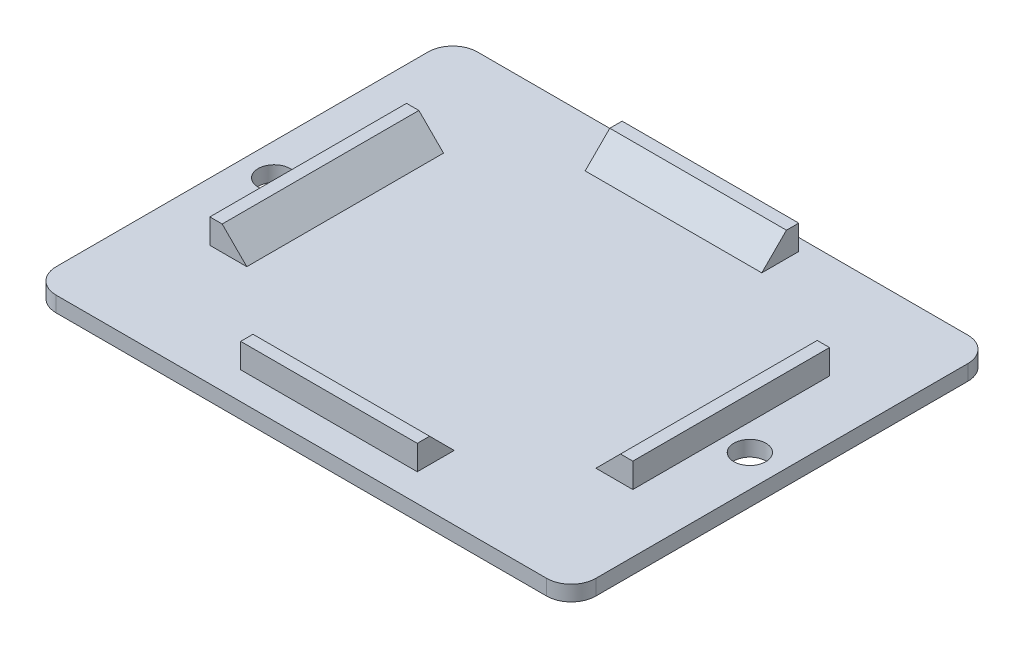
SolidWorks part; units mm, degrees
ref_plane "Plane XZ" through (0, 0, 0) normal (0, 0, 1) x (1, 0, 0)
ref_plane "Plane XY" through (0, 0, 0) normal (0, 1, 0) x (1, 0, 0)
ref_plane "Plane YZ" through (0, 0, 0) normal (1, 0, 0) x (0, 0, -1)
sketch "Sketch1" plane through (0, 0, 0) normal (0, 1, 0) x (1, 0, 0)
  line L0 (0, 22.225) -> (0, -22.225) construction
  line L1 (-28.3337, 22.225) -> (28.3337, 22.225)
  line L2 (-28.3337, 22.225) -> (-28.3337, -22.225)
  line L3 (-28.3337, -22.225) -> (28.3337, -22.225)
  line L4 (28.3337, 22.225) -> (28.3337, -22.225)
  dimension "D1" = 56.6674
  dimension "D2" = 44.45
extrude "Boss-Extrude1" add sketch "Sketch1" along normal blind 1.5875
sketch "Sketch2" plane through (0, 1.5875, 0) normal (0, 1, 0) x (1, 0, 0)
  line L0 (28.3337, 22.225) -> (-28.3337, 22.225) construction
  line L1 (-21.9837, 20.6375) -> (21.9837, 20.6375) construction
  line L2 (-21.9837, 20.6375) -> (-21.9837, -19.05) construction
  line L3 (-21.9837, -19.05) -> (21.9837, -19.05) construction
  line L4 (21.9837, 20.6375) -> (21.9837, -19.05) construction
  line L5 (28.3337, -22.225) -> (28.3337, 22.225) construction
  line L6 (-28.3337, 22.225) -> (-28.3337, -22.225) construction
  line L15 (-21.8059, 20.4597) -> (-21.8059, -18.8722)
  line L16 (-21.8059, -18.8722) -> (21.8059, -18.8722)
  line L17 (21.8059, 20.4597) -> (21.8059, -18.8722)
  line L18 (-21.8059, 20.4597) -> (21.8059, 20.4597)
  line L19 (-20.5359, 19.1897) -> (-20.5359, -17.6022)
  line L20 (-20.5359, -17.6022) -> (20.5359, -17.6022)
  line L21 (20.5359, 19.1897) -> (20.5359, -17.6022)
  line L22 (-20.5359, 19.1897) -> (20.5359, 19.1897)
  dimension "D1" = 43.9674
  dimension "D2" = 39.6875
  dimension "D3" = 1.5875
  dimension "D4" = 6.35
  dimension "D5" = 6.35
  dimension "D6" = 0.1778
  dimension "D7" = 1.27
extrude "Boss-Extrude2" add sketch "Sketch2" along normal blind 2.54
sketch "Sketch3" plane through (0, 1.5875, 0) normal (0, 1, 0) x (1, 0, 0)
  line L0 (-24.5237, 0) -> (24.5237, 0) construction
  circle A0 centre (-24.5237, 0) radius 1.651
  circle A1 centre (24.5237, 0) radius 1.651
  dimension "D1" = 3.302
  dimension "D2" = 3.302
  dimension "D3" = 49.0474
extrude "Cut-Extrude1" cut sketch "Sketch3" against normal through all
sketch "Sketch4" plane through (0, 1.5875, 0) normal (0, 1, 0) x (1, 0, 0)
  line L0 (27.8257, 21.717) -> (-27.8257, 21.717)
  line L1 (-27.8257, 21.717) -> (-27.8257, -21.717)
  line L2 (-27.8257, -21.717) -> (27.8257, -21.717)
  line L3 (27.8257, -21.717) -> (27.8257, 21.717)
  line L4 (-28.3337, 22.225) -> (-28.3337, -22.225)
  line L5 (-28.3337, -22.225) -> (28.3337, -22.225)
  line L6 (28.3337, -22.225) -> (28.3337, 22.225)
  line L7 (28.3337, 22.225) -> (-28.3337, 22.225)
  line L8 (-28.3337, 22.225) -> (-28.3337, -22.225)
  line L9 (-28.3337, -22.225) -> (28.3337, -22.225)
  line L10 (28.3337, -22.225) -> (28.3337, 22.225)
  line L11 (28.3337, 22.225) -> (-28.3337, 22.225)
  dimension "D1" = 0
  dimension "D2" = 0.508
extrude "Cut-Extrude2" cut sketch "Sketch4" against normal through all
fillet "Fillet1" radius 2.54 4 edges at (-27.8257, 0.7937, 21.717) (27.8257, 0.7937, 21.717) (27.8257, 0.7937, -21.717) (-27.8257, 0.7937, -21.717)
sketch "Sketch5" plane through (0, 1.5875, 0) normal (0, 1, 0) x (1, 0, 0)
  line L0 (-20.5359, 0.7937) -> (20.5359, 0.7937) construction
  line L1 (-21.8059, 20.4597) -> (-9.1059, 20.4597)
  line L2 (-21.8059, 20.4597) -> (-21.8059, 10.9347)
  line L3 (-21.8059, 10.9347) -> (-9.1059, 10.9347)
  line L4 (-9.1059, 20.4597) -> (-9.1059, 10.9347)
  line L5 (-20.5359, 19.1897) -> (-20.5359, -17.6022) construction
  line L6 (20.5359, -17.6022) -> (20.5359, 19.1897) construction
  line L7 (0, 0.7937) -> (0, -17.6022) construction
  line L8 (-20.5359, -17.6022) -> (20.5359, -17.6022) construction
  line L9 (-21.8059, -9.3472) -> (-9.1059, -9.3472)
  line L10 (-9.1059, -18.8722) -> (-9.1059, -9.3472)
  line L11 (-21.8059, -18.8722) -> (-9.1059, -18.8722)
  line L12 (-21.8059, -18.8722) -> (-21.8059, -9.3472)
  line L13 (21.8059, -18.8722) -> (21.8059, -9.3472)
  line L14 (21.8059, -18.8722) -> (9.1059, -18.8722)
  line L15 (9.1059, -18.8722) -> (9.1059, -9.3472)
  line L16 (21.8059, -9.3472) -> (9.1059, -9.3472)
  line L17 (21.8059, 10.9347) -> (9.1059, 10.9347)
  line L18 (9.1059, 20.4597) -> (9.1059, 10.9347)
  line L19 (21.8059, 20.4597) -> (9.1059, 20.4597)
  line L20 (21.8059, 20.4597) -> (21.8059, 10.9347)
  dimension "D1" = 9.525
  dimension "D2" = 12.7
extrude "Cut-Extrude3" cut sketch "Sketch5" along normal through all
chamfer "Chamfer1" distance 2.54 angle 45 4 edges at (0, 1.5875, 17.6022) (20.5359, 1.5875, -0.7937) (0, 1.5875, -19.1897) (-20.5359, 1.5875, -0.7937)
